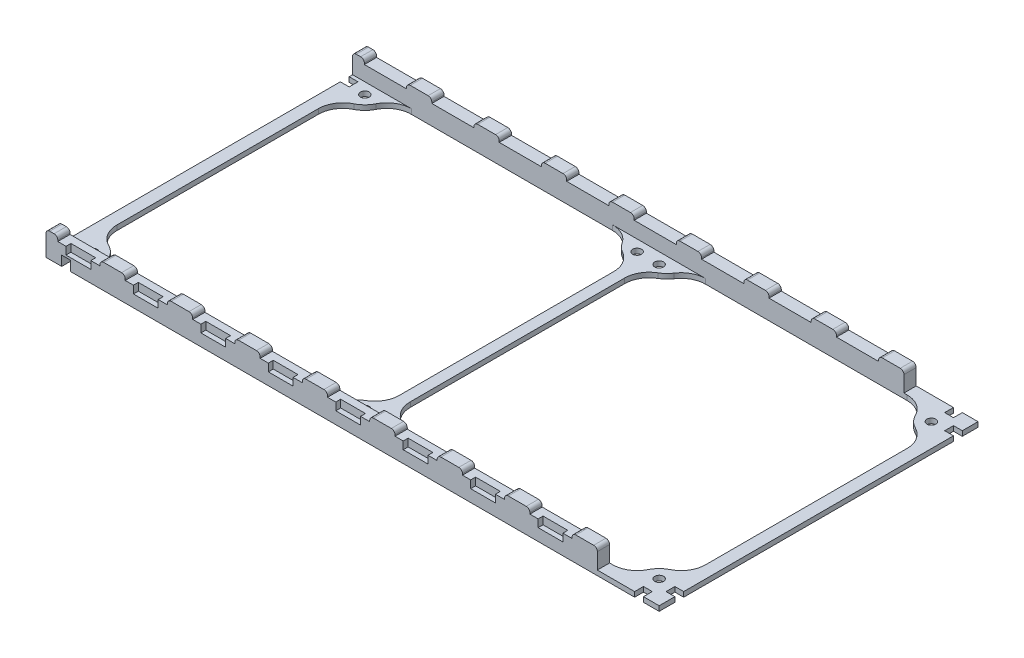
SolidWorks part; units mm, degrees
ref_plane "Front Plane" through (0, 0, 0) normal (0, 0, 1) x (1, 0, 0)
ref_plane "Top Plane" through (0, 0, 0) normal (0, 1, 0) x (1, 0, 0)
ref_plane "Right Plane" through (0, 0, 0) normal (1, 0, 0) x (0, 0, -1)
sketch "Sketch1" plane through (0, 0, 0) normal (0, 1, 0) x (1, 0, 0)
  line L1 (0, 0) -> (250, 0)
  line L2 (0, 0) -> (0, 130)
  line L3 (0, 130) -> (250, 130)
  line L4 (250, 0) -> (250, 130)
  line L5 (5, 5) -> (245, 5)
  line L6 (5, 5) -> (5, 125)
  line L7 (5, 125) -> (245, 125)
  line L8 (245, 5) -> (245, 125)
  dimension "D1" = 250
  dimension "D2" = 130
  dimension "D3" = 240
  dimension "D4" = 120
  dimension "D5" = 5
  dimension "D6" = 5
extrude "Boss-Extrude1" add sketch "Sketch1" along normal blind 2
sketch "Sketch2" plane through (0, 0, 0) normal (0, 1, 0) x (1, 0, 0)
  line L0 (245, 125) -> (5, 125) construction
  line L1 (5, 5) -> (14, 5)
  line L2 (5, 5) -> (5, 14)
  line L3 (5, 14) -> (14, 14)
  line L4 (14, 5) -> (14, 14)
  line L5 (5, 125) -> (14, 125)
  line L6 (5, 125) -> (5, 116)
  line L7 (5, 116) -> (14, 116)
  line L8 (14, 125) -> (14, 116)
  line L9 (116, 125) -> (125, 125)
  line L10 (116, 125) -> (116, 116)
  line L11 (116, 116) -> (125, 116)
  line L14 (5, 5) -> (245, 5) construction
  line L15 (125, 116) -> (134, 116)
  line L17 (125, 125) -> (134, 125)
  line L18 (134, 116) -> (134, 125)
  line L19 (116, 5) -> (134, 5)
  line L20 (116, 5) -> (116, 14)
  line L21 (116, 14) -> (134, 14)
  line L22 (134, 5) -> (134, 14)
  line L24 (245, 125) -> (236, 125)
  line L25 (245, 125) -> (245, 116)
  line L26 (245, 116) -> (236, 116)
  line L27 (236, 125) -> (236, 116)
  line L28 (245, 5) -> (236, 5)
  line L29 (245, 5) -> (245, 14)
  line L30 (245, 14) -> (236, 14)
  line L31 (236, 5) -> (236, 14)
  circle A0 centre (9.5, 9.5) radius 1.8
  circle A1 centre (9.5, 120.5) radius 1.8
  circle A2 centre (120.5, 120.5) radius 1.8
  circle A3 centre (129.5, 120.5) radius 1.8
  circle A4 centre (120.5, 9.5) radius 1.8
  circle A5 centre (129.5, 9.5) radius 1.8
  circle A6 centre (240.5, 120.5) radius 1.8
  circle A7 centre (240.5, 9.5) radius 1.8
  dimension "D9" = 3.6
  dimension "D10" = 3.6
  dimension "D12" = 3.6
  dimension "D18" = 3.6
  dimension "D16" = 3.6
  dimension "D23" = 3.6
  dimension "D27" = 3.6
  dimension "D32" = 3.6
  dimension "D2" = 4.5
  dimension "D3" = 4.5
  dimension "D4" = 4.5
  dimension "D5" = 4.5
  dimension "D6" = 4.5
  dimension "D7" = 4.5
  dimension "D8" = 4.5
  dimension "D11" = 4.5
  dimension "D13" = 4.5
  dimension "D14" = 4.5
  dimension "D15" = 4.5
  dimension "D17" = 4.5
  dimension "D19" = 4.5
  dimension "D20" = 4.5
  dimension "D21" = 4.5
  dimension "D22" = 4.5
  dimension "D24" = 9
  dimension "D25" = 4.5
  dimension "D26" = 120
  dimension "D28" = 4.5
  dimension "D29" = 4.5
  dimension "D30" = 4.5
  dimension "D31" = 4.5
  dimension "D33" = 4.5
  dimension "D34" = 4.5
  dimension "D35" = 4.5
  dimension "D36" = 4.5
extrude "Boss-Extrude2" add sketch "Sketch2" along normal blind 2
fillet "Fillet1" radius 10 12 edges at (5, 1, -14) (14, 1, -5) (5, 1, -116) (14, 1, -125) (116, 1, -125) (134, 1, -125) (245, 1, -116) (236, 1, -125) (245, 1, -14) (236, 1, -5) (116, 1, -5) (134, 1, -5)
fillet "Fillet2" radius 10 8 edges at (14, 1, -14) (116, 1, -14) (134, 1, -14) (236, 1, -14) (236, 1, -116) (134, 1, -116) (116, 1, -116) (14, 1, -116)
sketch "Sketch3" plane through (0, 0, 0) normal (0, 1, 0) x (1, 0, 0)
  line L1 (122.7534, 116) -> (127.2466, 116)
  line L2 (122.7534, 116) -> (122.7534, 14)
  line L3 (122.7534, 14) -> (127.2466, 14)
  line L4 (127.2466, 116) -> (127.2466, 14)
extrude "Boss-Extrude3" add sketch "Sketch3" along normal blind 2
fillet "Fillet3" radius 10 4 edges at (122.7534, 1, -116) (127.2466, 1, -116) (127.2466, 1, -14) (122.7534, 1, -14)
sketch "Sketch4" plane through (0, 2, 0) normal (0, 1, 0) x (1, 0, 0)
  line L0 (0, 130) -> (0, 0) construction
  line L1 (4.8, 0) -> (22, 0)
  line L2 (4.8, 0) -> (4.8, 5)
  line L3 (4.8, 5) -> (22, 5)
  line L4 (22, 0) -> (22, 5)
  line L5 (4.8, 130) -> (22, 130)
  line L6 (4.8, 130) -> (4.8, 125)
  line L7 (4.8, 125) -> (22, 125)
  line L8 (22, 130) -> (22, 125)
  dimension "D1" = 17.2
  dimension "D2" = 5
  dimension "D3" = 5
  dimension "D4" = 17.2
  dimension "D5" = 4.8
  dimension "D6" = 4.8
extrude "Boss-Extrude4" add sketch "Sketch4" along normal blind 6
sketch "Sketch5" plane through (0, 2, 0) normal (0, 1, 0) x (1, 0, 0)
  line L0 (106.0501, 125) -> (23.9499, 125) construction
  line L1 (22, 130) -> (32.3, 130)
  line L2 (22, 130) -> (22, 125)
  line L3 (22, 125) -> (32.3, 125)
  line L4 (32.3, 130) -> (32.3, 125)
  line L6 (22, 0) -> (250, 0) construction
  line L7 (22, 5) -> (32.3, 5)
  line L8 (22, 5) -> (22, 0)
  line L9 (22, 0) -> (32.3, 0)
  line L10 (32.3, 5) -> (32.3, 0)
  line L12 (4.8, 5) -> (4.8, 0) construction
  line L13 (4.8, 130) -> (4.8, 125) construction
  dimension "D1" = 10.3
  dimension "D2" = 10.3
  dimension "D3" = 17.2
  dimension "D4" = 17.2
extrude "Boss-Extrude5" add sketch "Sketch5" along normal blind 8
fillet "Fillet4" radius 1.5 4 edges at (22, 10, -2.5) (32.3, 10, -2.5) (32.3, 10, -127.5) (22, 10, -127.5)
sketch "Sketch6" plane through (0, 2, 0) normal (0, 1, 0) x (1, 0, 0)
  line L1 (0, 130) -> (4.8, 130)
  line L2 (0, 130) -> (0, 125)
  line L3 (0, 125) -> (4.8, 125)
  line L4 (4.8, 130) -> (4.8, 125)
  line L5 (0, 0) -> (4.8, 0)
  line L6 (0, 0) -> (0, 5)
  line L7 (0, 5) -> (4.8, 5)
  line L8 (4.8, 0) -> (4.8, 5)
  dimension "D1" = 4.8
  dimension "D2" = 5
  dimension "D3" = 5
  dimension "D4" = 4.8
extrude "Boss-Extrude6" add sketch "Sketch6" along normal blind 8
sketch "Sketch10" plane through (0, 0, 0) normal (0, 0, 1) x (1, 0, 0)
  line L0 (4.8, 8) -> (22, 8) construction
  line L1 (8.15, 8) -> (18.25, 8)
  line L2 (8.15, 8) -> (8.15, 4.9)
  line L3 (8.15, 4.9) -> (18.25, 4.9)
  line L4 (18.25, 8) -> (18.25, 4.9)
  line L6 (4.8, 10) -> (4.8, 8) construction
  dimension "D1" = 10.1
  dimension "D2" = 3.1
  dimension "D3" = 3.35
extrude "Cut-Extrude2" cut sketch "Sketch10" against normal blind 2
pattern_linear "LPattern1" count 8 spacing 27.5 along (1, 0, 0) of "Boss-Extrude4", "Boss-Extrude5", "Fillet4"
fillet "Fillet5" radius 1.5 4 edges at (0, 10, -127.5) (4.8, 10, -127.5) (0, 10, -2.5) (4.8, 10, -2.5)
sketch "Sketch9" plane through (0, 0, 0) normal (0, 1, 0) x (1, 0, 0)
  line L5 (0, 0) -> (0, 5) construction
  line L7 (10, 3.6) -> (6.4, 3.6)
  line L8 (10, 3.6) -> (10, 0)
  line L9 (10, 0) -> (6.4, 0)
  line L10 (6.4, 3.6) -> (6.4, 0)
  line L11 (1.5, 0) -> (3.3, 0) construction
  line L12 (3.6, 10) -> (0, 10)
  line L13 (3.6, 10) -> (3.6, 6.4)
  line L14 (3.6, 6.4) -> (0, 6.4)
  line L15 (0, 10) -> (0, 6.4)
  line L16 (8.15, 0) -> (18.25, 0) construction
  line L17 (0, 125) -> (0, 5) construction
  dimension "D1" = 3.6
  dimension "D2" = 0
  dimension "D3" = 0
  dimension "D5" = 3.6
  dimension "D6" = 3.6
  dimension "D7" = 10
  dimension "D8" = 3.6
  dimension "D9" = 10
extrude "Cut-Extrude1" cut sketch "Sketch9" along normal blind 4
ref_plane "Plane1" through (125, 0, 0) normal (-1, 0, 0) x (0, 0, 1)
ref_plane "Plane2" through (0, 0, -65) normal (0, 0, 1) x (1, 0, 0)
mirror "Mirror1" about plane through (0, 0, -65) normal (0, 0, 1) of "Cut-Extrude1" second plane through (125, 0, 0) second plane normal (-1, 0, 0)
pattern_linear "LPattern2" count 8 spacing 27.5 along (1, 0, 0) of "Cut-Extrude2"
